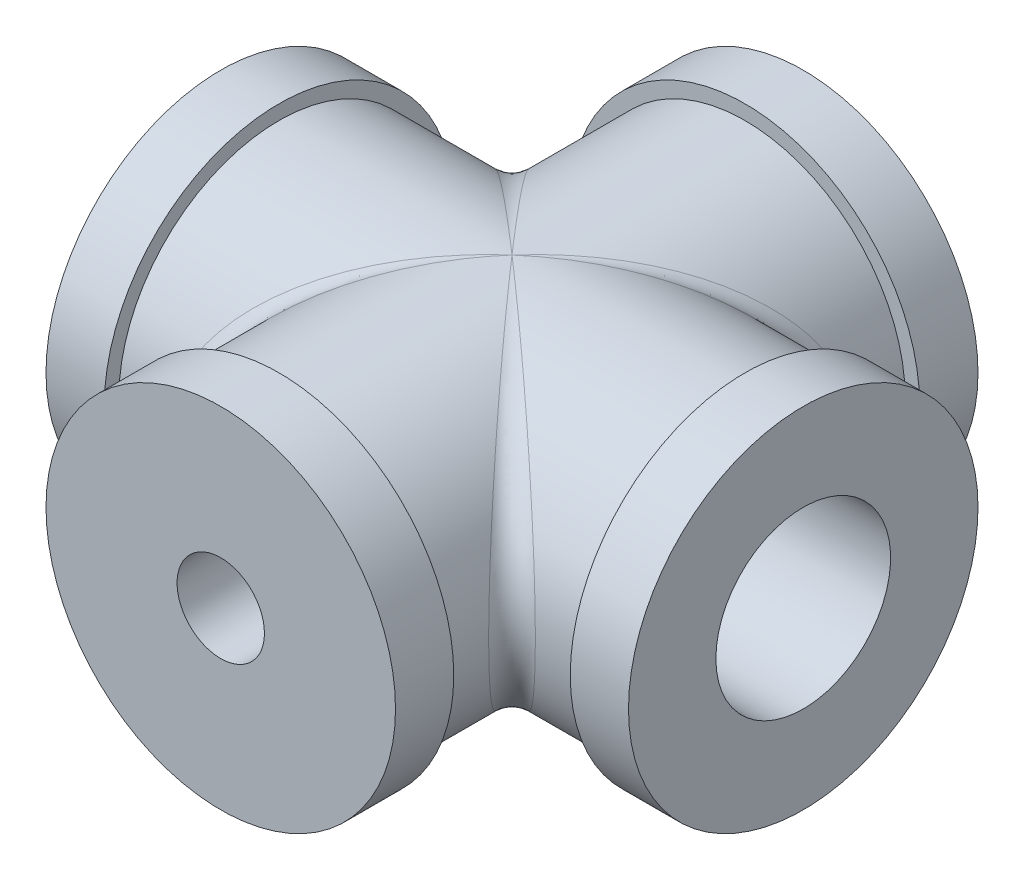
SolidWorks part; units mm, degrees
ref_plane "Front Plane" through (0, 0, 0) normal (0, 0, 1) x (1, 0, 0)
ref_plane "Top Plane" through (0, 0, 0) normal (0, 1, 0) x (1, 0, 0)
ref_plane "Right Plane" through (0, 0, 0) normal (1, 0, 0) x (0, 0, -1)
sketch "Sketch4" plane through (0, 0, 0) normal (0, 0, 1) x (1, 0, 0)
  line L0 (-50, 30) -> (-50, 15)
  line L1 (-50, 15) -> (50, 15)
  line L2 (50, 15) -> (50, 30)
  line L3 (50, 30) -> (40, 30)
  line L4 (40, 30) -> (40, 27.5)
  line L5 (40, 27.5) -> (-40, 27.5)
  line L6 (-40, 27.5) -> (-40, 30)
  line L7 (-40, 30) -> (-50, 30)
  line L8 (-122.3437, 0) -> (87.6562, 0) construction
  dimension "D1" = 30
  dimension "D2" = 55
  dimension "D3" = 60
  dimension "D4" = 60
  dimension "D5" = 50
  dimension "D6" = 50
  dimension "D7" = 10
  dimension "D8" = 10
revolve "Revolve1" add sketch "Sketch4" angle 360 about L8 other way angle 360
sketch "Sketch6" plane through (0, 0, 0) normal (1, 0, 0) x (0, 0, -1)
  line L0 (-43.0756, 0) -> (43.0756, 0) construction
  line L1 (0, 47.2195) -> (0, -48.3825) construction
  line L2 (-50, 7.5) -> (50, 7.5)
  line L3 (50, 7.5) -> (50, 30)
  line L4 (50, 30) -> (40, 30)
  line L5 (40, 30) -> (40, 27.5)
  line L6 (40, 27.5) -> (-40, 27.5)
  line L7 (-40, 27.5) -> (-40, 30)
  line L8 (-40, 30) -> (-50, 30)
  line L9 (-50, 30) -> (-50, 7.5)
  dimension "D1" = 60
  dimension "D2" = 55
  dimension "D3" = 15
  dimension "D4" = 10
  dimension "D5" = 60
  dimension "D6" = 10
  dimension "D7" = 50
  dimension "D8" = 100
revolve "Revolve2" add sketch "Sketch6" angle 360 about L0
sketch "Sketch7" plane through (0, 0, 0) normal (1, 0, 0) x (0, 0, -1)
  circle A0 centre (0, 0) radius 15
  dimension "D1" = 30
extrude "Cut-Extrude1" cut sketch "Sketch7" against normal mid plane 100
sketch "Sketch8" plane through (0, 0, 0) normal (0, 0, 1) x (1, 0, 0)
  circle A0 centre (0, 0) radius 7.5
extrude "Cut-Extrude2" cut sketch "Sketch8" against normal mid plane 100
fillet "Fillet1" radius 4 4 edges at (27.5, 0, -27.5) (-27.5, 0, -27.5) (-27.5, 0, 27.5) (27.5, 0, 27.5)
